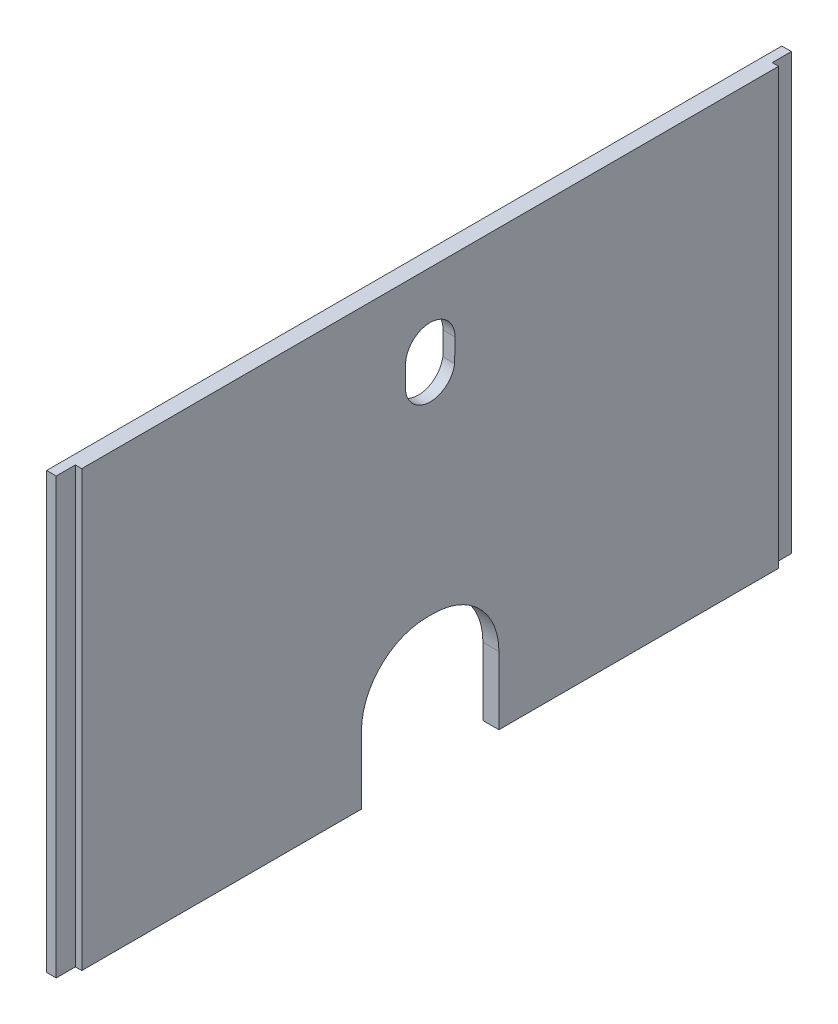
SolidWorks part; units mm, degrees
ref_plane "정면" through (0, 0, 0) normal (0, 0, 1) x (1, 0, 0)
ref_plane "윗면" through (0, 0, 0) normal (0, 1, 0) x (1, 0, 0)
ref_plane "우측면" through (0, 0, 0) normal (1, 0, 0) x (0, 0, -1)
sketch "스케치1" plane through (0, 0, 0) normal (1, 0, 0) x (0, 0, -1)
  line L1 (-60, 34) -> (60, 34)
  line L2 (-60, 34) -> (-60, -34)
  line L3 (-60, -34) -> (60, -34)
  line L4 (60, 34) -> (60, -34)
  line L5 (-60, 34) -> (60, -34) construction
  line L6 (-60, -34) -> (60, 34) construction
  point P0 (0, 0)
  dimension "D1" = 120
  dimension "D2" = 68
extrude "보스-돌출1" add sketch "스케치1" along normal blind 3
sketch "스케치2" plane through (0, 34, 0) normal (0, 1, 0) x (1, 0, 0)
  line L0 (0.5, -57.5) -> (2, -57.5)
  line L2 (2, -57.5) -> (2, -54.5)
  line L3 (2, -54.5) -> (3, -54.5)
  line L4 (3, 60) -> (3, -60) construction
  line L5 (3, -54.5) -> (3, -60)
  line L6 (3, -60) -> (0.5, -60)
  line L7 (0.5, -60) -> (0.5, -57.5)
  line L8 (0, 0) -> (3, 0) construction
  line L9 (0.5, 60) -> (0.5, 57.5)
  line L10 (3, 60) -> (0.5, 60)
  line L11 (3, 54.5) -> (3, 60)
  line L12 (2, 54.5) -> (3, 54.5)
  line L13 (2, 57.5) -> (2, 54.5)
  line L14 (0.5, 57.5) -> (2, 57.5)
  line L16 (0.5, 60) -> (0, 60)
  line L17 (0.5, 60) -> (0.5, -60)
  line L18 (0.5, -60) -> (0, -60)
  line L19 (0, 60) -> (0, -60)
  line M1 (0, 60) -> (0, -60)
  line M2 (0, -60) -> (3, -60)
  line M3 (3, -60) -> (3, 60)
  line M4 (3, 60) -> (0, 60)
  dimension "D1" = 1
  dimension "D2" = 3
  dimension "D3" = 2.5
  dimension "D4" = 1.5
extrude "컷-돌출1" cut sketch "스케치2" against normal through all contours L8 L19 L7 L17 M2 | L7 L3 L2 L0 M2 M3 | L9 L14 L13 L12 M3 M4 | L8 L17 L9 M1 M4 region at (1.9932, 34, 57.8581) region at (0.25, 34, 30) region at (0.25, 34, -30) region at (1.9932, 34, -57.8581)
sketch "스케치7" plane through (3, 0, 0) normal (1, 0, 0) x (0, 0, -1)
  line L0 (9.5, -23.3838) -> (-25, -23.3838) construction
  line L1 (-0.5, -13.1338) -> (0.5, -13.1338)
  line L2 (-10.75, -23.3838) -> (-10.75, -34)
  line L3 (-54.5, -34) -> (54.5, -34) construction
  line L4 (10.75, -23.3838) -> (10.75, -34)
  line L5 (10.75, -34) -> (-10.75, -34)
  arc A0 (-0.5, -13.1338) -> (-10.75, -23.3838) centre (-0.5, -23.3838) ccw
  arc A1 (10.75, -23.3838) -> (0.5, -13.1338) centre (0.5, -23.3838) ccw
  line M3 (-54.5, -34) -> (54.5, -34)
  dimension "D1" = 20.5
  dimension "D2" = 20.5
  dimension "D3" = 1
  dimension "D4" = 1
extrude "컷-돌출7" cut sketch "스케치7" against normal up to surface (2.5 mm away) contours L4 A1 L1 A0 L2 M3 region at (3, -24.4769, 0) up to face at (0.5, 0, 0)
sketch "스케치14" plane through (0.5, 0, 0) normal (-1, 0, 0) x (0, 0, 1)
  line L0 (-57.5, 2.5) -> (57.5, 2.5)
  line L1 (-57.5, -34) -> (-57.5, 34) construction
  line L2 (57.5, -34) -> (57.5, 34) construction
  line L3 (57.5, 34) -> (-57.5, 34) construction
  line L4 (-12.5, 28.5) -> (12.5, 28.5)
  line L5 (0, 2.5) -> (0, 34) construction
  line L6 (12.5, 28.5) -> (12.5, 4.5)
  line L7 (12.5, 4.5) -> (-12.5, 4.5)
  line L8 (-12.5, 28.5) -> (-12.5, 4.5)
  point P15 (0, 4.5)
  point P16 (0, 28.5)
  dimension "D1" = 31.5
  dimension "D2" = 2
  dimension "D3" = 24
  dimension "D4" = 12.5
sketch "스케치16" plane through (3, 0, 0) normal (1, 0, 0) x (0, 0, -1)
  line L0 (-4.5, 26.55) -> (4.5, 26.55)
  line L5 (4.5, 26.55) -> (4.5, 14.55)
  line L6 (-4.5, 14.55) -> (4.5, 14.55)
  line L7 (-4.5, 26.55) -> (-4.5, 14.55)
  line L8 (0, 19.6662) -> (0, 22.6662)
  line L9 (0, 2.5) -> (0, 34) construction
  line L10 (-3.875, 22.6662) -> (-3.8269, 19.0576)
  line L11 (3.875, 22.6662) -> (3.8269, 19.0576)
  arc A0 (-3.8269, 19.0576) -> (3.8269, 19.0576) centre (0, 19.6662) ccw
  arc A1 (3.875, 22.6662) -> (-3.875, 22.6662) centre (0, 22.6662) ccw
  dimension "D1" = 7.75
  dimension "D3" = 7.75
  dimension "D2" = 3
  dimension "D4" = 12
extrude "컷-돌출10" cut sketch "스케치16" against normal up to surface (2.5 mm away) contours L11 A1 L10 A0 region at (3, 26.4087, 0) up to face at (0.5, -13.679, 0)
sketch "스케치17" plane through (0.5, 0, 0) normal (-1, 0, 0) x (0, 0, 1)
  line L1 (-4.5, 26.55) -> (4.5, 26.55)
  line L2 (-4.5, 26.55) -> (-4.5, 14.55)
  line L3 (-4.5, 14.55) -> (4.5, 14.55)
  line L4 (4.5, 26.55) -> (4.5, 14.55)
extrude "컷-돌출11" cut sketch "스케치17" against normal blind 0.65
sketch "스케치18" plane through (0.5, 0, 0) normal (-1, 0, 0) x (0, 0, 1)
  line L0 (-14.75, 4.5) -> (14.75, 4.5)
  line L1 (14.75, 4.5) -> (14.75, 2.5)
  line L2 (-57.5, 2.5) -> (57.5, 2.5) construction
  line L3 (0, 4.5) -> (0, 2.5) construction
  line L4 (-14.75, 4.5) -> (-14.75, 2.5)
  line L5 (-12.5, 4.5) -> (12.5, 4.5)
  line L6 (-14.75, 2.5) -> (14.75, 2.5)
  dimension "D1" = 14.75
extrude "보스-돌출2" add sketch "스케치18" along normal blind 8 contours L3 L0 L4 L6 | L5 L3 L6 L1 L0 region at (0.5, 3.5, -7.375) region at (0.5, 3.5, 7.375)
sketch "스케치19" plane through (0, 4.5, 0) normal (0, 1, 0) x (1, 0, 0)
  line L0 (0.5, 14.75) -> (0.5, 6)
  line L1 (0.5, -57.5) -> (0.5, 57.5) construction
  line L2 (0.5, 6) -> (-1.9355, 6)
  line L3 (-1.9355, 6) -> (-1.9355, 13)
  line L4 (-1.9355, 13) -> (-3.9355, 13)
  line L5 (-3.9355, 13) -> (-3.9355, -13)
  line L6 (-3.9355, -13) -> (-1.9355, -13)
  line L7 (-1.9355, -13) -> (-1.9355, -5)
  line L8 (-1.9355, -5) -> (0.5, -5)
  line L9 (0.5, -5) -> (0.5, -14.75)
  line L10 (0.5, -14.75) -> (-7.5, -14.75)
  line L11 (-7.5, -14.75) -> (-7.5, 14.75)
  line L12 (-7.5, 14.75) -> (0.5, 14.75)
  line L13 (-2.4355, 10.5) -> (-2.4355, -10.5) construction
  line L14 (-3.4355, 10.5) -> (-3.4355, -10.5) construction
  line L15 (-3.4355, 12.5) -> (-2.4355, 12.5) construction
  line L16 (-3.4355, -12.5) -> (-2.4355, -12.5) construction
  line L17 (-5.9355, 14.75) -> (-5.9355, -14.75)
  line M13 (0.5, -14.75) -> (0.5, 14.75)
  line M14 (0.5, 14.75) -> (-7.5, 14.75)
  line M15 (-7.5, 14.75) -> (-7.5, -14.75)
  line M16 (-7.5, -14.75) -> (0.5, -14.75)
  dimension "D1" = 0.5
  dimension "D2" = 0.5
  dimension "D3" = 0.5
  dimension "D4" = 0.5
  dimension "D5" = 0.5
  dimension "D6" = 7
  dimension "D7" = 8
  dimension "D8" = 2
extrude "컷-돌출12" cut sketch "스케치19" against normal blind 8 contours L17 L12 M15 M16 region at (-6.7177, 4.5, 0)
extrude "보스-돌출3" add sketch "스케치19<3>" along normal blind 3 contours L17 L10 L8 L7 L6 L5 L4 L3 L2 M14 M13 region at (0.1981, 4.5, -10.375)
sketch "스케치19<3>" plane through (0, 4.5, 0) normal (0, 1, 0) x (1, 0, 0) same geometry as "스케치19"
